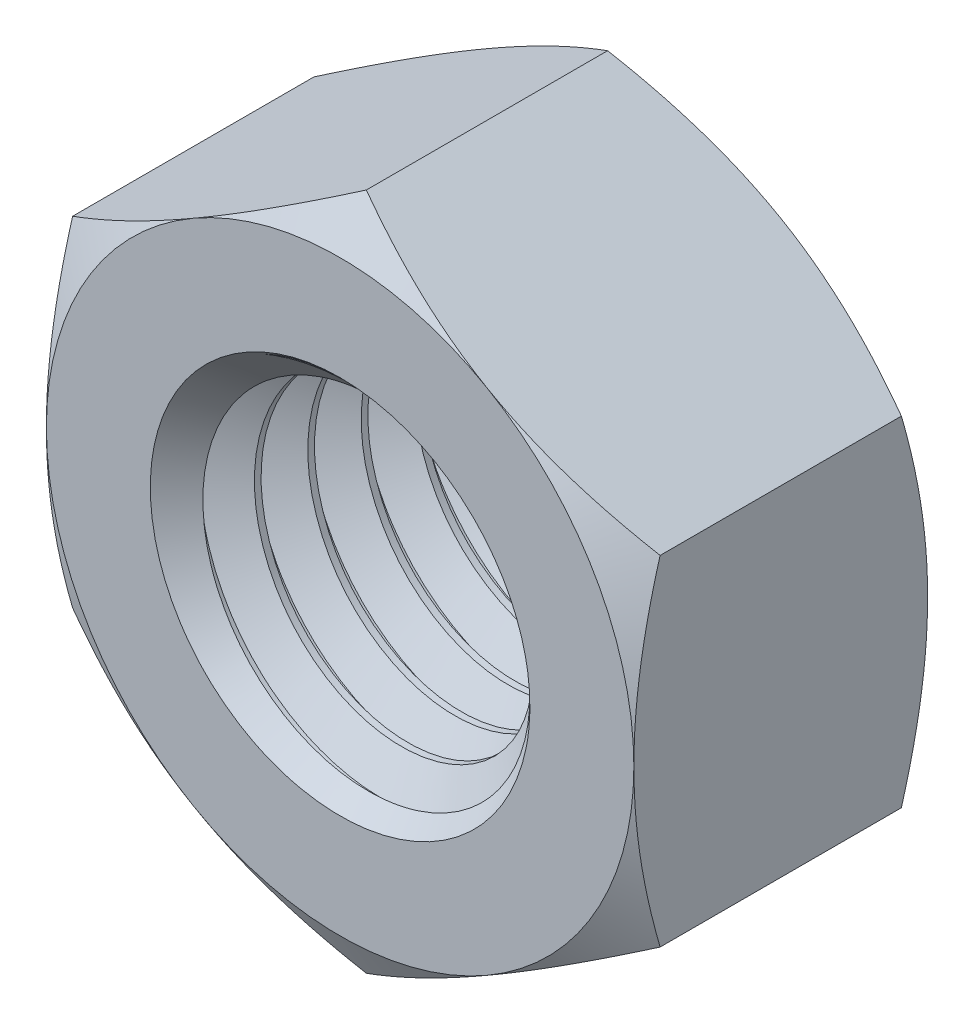
SolidWorks part; units mm, degrees
ref_plane "Front Plane" through (0, 0, 0) normal (0, 0, 1) x (1, 0, 0)
ref_plane "Top Plane" through (0, 0, 0) normal (0, 1, 0) x (1, 0, 0)
ref_plane "Right Plane" through (0, 0, 0) normal (1, 0, 0) x (0, 0, -1)
sketch "Sketch1" plane through (0, 0, 0) normal (1, 0, 0) x (0, 0, -1)
  line L0 (-5.5, 0) -> (5.5, 0) construction
  line L1 (-5.5, -11) -> (-5.5, 11) construction
  line L2 (5.5, -11) -> (5.5, 11) construction
  line L3 (-5.5, -7) -> (-5.5, 7) construction
  line L4 (-7.375, 7.2165) -> (-6.375, 5.4845) construction
  line L5 (-6.375, 5.4845) -> (-5.375, 7.2165) construction
  line L6 (-5.375, 7.2165) -> (-7.375, 7.2165) construction
  line L7 (-7.3125, 7.1083) -> (-5.4375, 7.1083) construction
  line L8 (-7.25, 7) -> (-5.5, 7) construction
  line L9 (-6.5, 5.701) -> (-6.25, 5.701) construction
  line L10 (-6.375, 5.701) -> (-6.375, 5.4845) construction
  line L11 (-6.375, 7.2165) -> (-6.375, 7) construction
  point P4 (0, 0)
  point P7 (-5.5, 0)
  point P11 (5.5, 0)
  point P14 (-5.5, 0)
  point P26 (-6.375, 7.1083)
  point P27 (-5.5, -7)
  dimension "Height" = 11
  dimension "Width" = 22
  dimension "Thread OD" = 14
  dimension "D1" = 60
  dimension "Pitch" = 2
  dimension "D2" = 0.25
sketch "Sketch2" plane through (0, 0, 0) normal (0, 0, 1) x (1, 0, 0)
  line L1 (0, 12.7017) -> (-11, 6.3509)
  line L2 (-11, 6.3509) -> (-11, -6.3509)
  line L3 (-11, -6.3509) -> (0, -12.7017)
  line L4 (0, -12.7017) -> (11, -6.3509)
  line L5 (11, -6.3509) -> (11, 6.3509)
  line L6 (11, 6.3509) -> (0, 12.7017)
  circle A0 centre (0, 0) radius 11 construction
  circle A1 centre (0, 0) radius 7
extrude "Boss-Extrude1" add sketch "Sketch2" along normal up to vertex (5.5 mm away) and the other way up to vertex (5.5 mm away) up to point (0, -11, 5.5) other way up to point (0, -11, -5.5)
sketch "Sketch3" plane through (0, 0, 5.5) normal (0, 0, 1) x (1, 0, 0)
  circle A0 centre (0, 0) radius 11
extrude "Cut-Extrude1" cut sketch "Sketch3" against normal through all draft 60 flip side to cut
mirror "Mirror1" about plane through (0, 0, 0) normal (0, 0, 1) of "Cut-Extrude1"
ref_axis "Center Axis 1" through (0, 0, -10.9016) along (0, 0, 1)
ref_plane "Contact Plane 1" through (0, 0, 5.5) normal (0, 0, 1) x (1, 0, 0)
ref_plane "Contact Plane 2" through (0, 0, -5.5) normal (0, 0, -1) x (-1, 0, 0)
sketch "Sketch4" plane through (0, 0, 0) normal (1, 0, 0) x (0, 0, -1)
  line L1 (-7.3125, 7.1083) -> (-6.5, 5.701)
  line L2 (-6.5, 5.701) -> (-6.25, 5.701)
  line L3 (-6.25, 5.701) -> (-5.4375, 7.1083)
  line L4 (-7.3125, 7.1083) -> (-5.4375, 7.1083) construction
  line L5 (-7.3125, 7.1083) -> (-5.4375, 7.1083)
sketch "Sketch5" plane through (0, 0, 5.5) normal (0, 0, 1) x (1, 0, 0)
  circle A0 centre (0, 0) radius 7 construction
  circle A1 centre (0, 0) radius 7
curve "Helix/Spiral1" pitch 2 height 13 radius 7 centre (0, 0, 5.5) axis (0, 0, -1) start towards (0, 1, 0)
sweep "Sweep1" add profiles "Sketch4" path "Helix/Spiral1"
sketch "Sketch6" plane through (0, 0, 5.5) normal (0, 0, 1) x (1, 0, 0)
  circle A1 centre (0, 0) radius 7.1083
extrude "Cut-Extrude2" cut sketch "Sketch6" along normal through all and the other way through all draft 45
sketch "Sketch7" plane through (0, 0, -5.5) normal (0, 0, -1) x (-1, 0, 0)
  circle A1 centre (0, 0) radius 7.1083
  circle A2 centre (0, 0) radius 7.1083
  dimension "D1" = 0
extrude "Cut-Extrude3" cut sketch "Sketch7" along normal through all and the other way through all draft 45
equation "\"D2@Sketch1\"=\"Pitch@Sketch1\"/8"
equation "\"D4@Helix/Spiral1\"=\"Pitch@Sketch1\""
equation "\"D3@Helix/Spiral1\"=\"Height@Sketch1\"+\"Pitch@Sketch1\""
